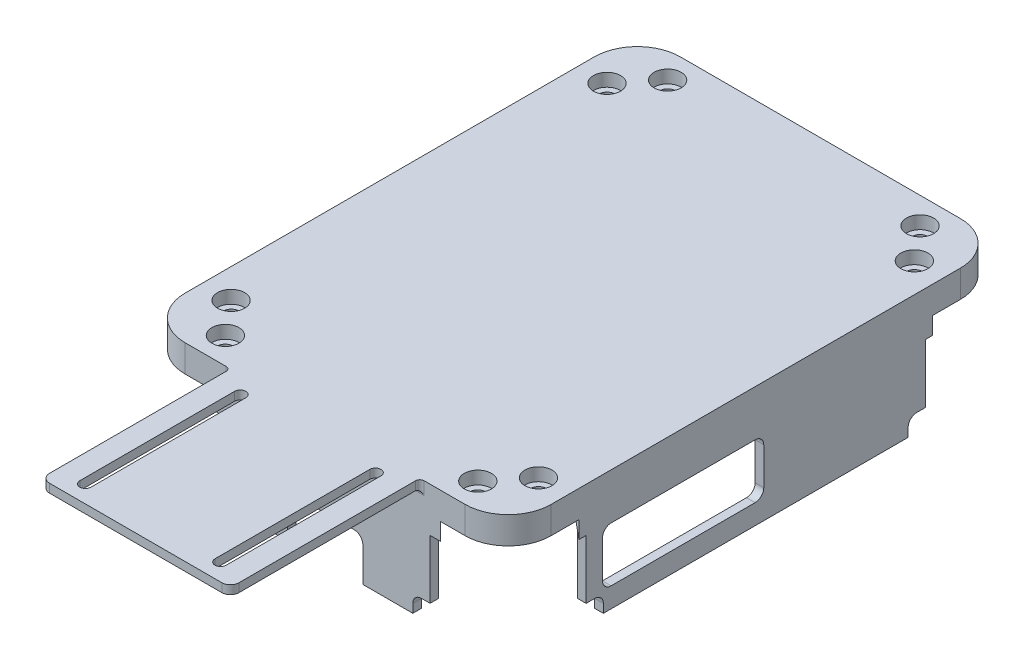
SolidWorks part; units mm, degrees
note: '?' marks a value the reader was unsure of.
material "3-D Printed ABS"
ref_plane "Front Plane" through (0, 0, 0) normal (0, 0, 1) x (1, 0, 0)
ref_plane "Top Plane" through (0, 0, 0) normal (0, 1, 0) x (1, 0, 0)
ref_plane "Right Plane" through (0, 0, 0) normal (1, 0, 0) x (0, 0, -1)
sketch "Sketch1" plane through (0, 0, 0) normal (0, 1, 0) x (1, 0, 0)
  line L1 (-53.975, -73.025) -> (53.975, -73.025)
  line L2 (-53.975, -73.025) -> (-53.975, 73.025)
  line L3 (-53.975, 73.025) -> (53.975, 73.025)
  line L4 (53.975, -73.025) -> (53.975, 73.025)
  line L5 (-53.975, -73.025) -> (53.975, 73.025) construction
  line L6 (-53.975, 73.025) -> (53.975, -73.025) construction
  point P0 (0, 0)
  dimension "D1" = 107.95
  dimension "D2" = 146.05
extrude "Boss-Extrude1" add sketch "Sketch1" against normal blind 2.54
sketch "Sketch13" plane through (0, 0, 0) normal (0, 1, 0) x (1, 0, 0)
  line L0 (0, 155.0212) -> (0, -155.0212) construction
  line L1 (0, 0) -> (-92.0171, 0) construction
  line L2 (53.975, -73.025) -> (53.975, 73.025) construction
  line L3 (53.975, -73.025) -> (28.575, -73.025)
  line L4 (53.975, -73.025) -> (53.975, -47.625)
  line L5 (53.975, -47.625) -> (28.575, -47.625)
  line L6 (28.575, -73.025) -> (28.575, -47.625)
  line L7 (-53.975, -73.025) -> (53.975, -73.025) construction
  line L8 (-28.575, -73.025) -> (-28.575, -47.625)
  line L9 (-53.975, -47.625) -> (-28.575, -47.625)
  line L10 (-53.975, -73.025) -> (-53.975, -47.625)
  line L11 (-53.975, -73.025) -> (-28.575, -73.025)
  line L12 (-53.975, 73.025) -> (-28.575, 73.025)
  line L13 (-53.975, 73.025) -> (-53.975, 47.625)
  line L14 (-53.975, 47.625) -> (-28.575, 47.625)
  line L15 (-28.575, 73.025) -> (-28.575, 47.625)
  line L16 (28.575, 73.025) -> (28.575, 47.625)
  line L17 (53.975, 47.625) -> (28.575, 47.625)
  line L18 (53.975, 73.025) -> (53.975, 47.625)
  line L19 (53.975, 73.025) -> (28.575, 73.025)
  dimension "D1" = 25.4
  dimension "D2" = 25.4
extrude "Boss-Extrude4" add sketch "Sketch13" against normal blind 13.0835
sketch "Sketch2" plane through (0, 0, 0) normal (0, 1, 0) x (1, 0, 0)
  line L0 (0, 0) -> (100.1618, 0) construction
  line L1 (0, 0) -> (0, 86.3534) construction
  line L2 (53.975, 73.025) -> (-53.975, 73.025) construction
  line L3 (-53.975, 73.025) -> (-53.975, -73.025) construction
  line L4 (0, 0) -> (-53.975, 73.025) construction
  line L5 (0, 0) -> (-152.4, 0) construction
  line L6 (-152.4, 0) -> (-152.4, 152.4) construction
  line L7 (-152.4, 152.4) -> (0, 152.4) construction
  line L8 (0, 152.4) -> (0, 86.3534) construction
  line L9 (-152.4, 152.4) -> (0, 0) construction
  line L10 (-152.4, 152.4) -> (-41.275, 60.325) construction
  line L11 (-41.275, 60.325) -> (0, 26.1257) construction
  line L13 (-53.975, 44.9974) -> (-30.7521, 73.025) construction
  circle A0 centre (45.3264, 55.4354) radius 3.302
  circle A1 centre (37.2236, 65.2146) radius 3.302
  circle A2 centre (45.3264, -55.4354) radius 3.302
  circle A3 centre (37.2236, -65.2146) radius 3.302
  circle A4 centre (-37.2236, 65.2146) radius 3.302
  circle A5 centre (-45.3264, 55.4354) radius 3.302
  circle A6 centre (-45.3264, -55.4354) radius 3.302
  circle A7 centre (-37.2236, -65.2146) radius 3.302
  point P15 (-41.275, 60.325)
  dimension "D1" = 6.35
  dimension "D3" = 12.7
  dimension "D4" = 6.604
  dimension "D5" = 6.604
  dimension "D2" = 12.7
  dimension "D6" = 6.35
extrude "Cut-Extrude1" cut sketch "Sketch2" against normal through all
sketch "Sketch3" plane through (0, 0, 0) normal (0, 1, 0) x (1, 0, 0)
  line L0 (-53.975, 25.4) -> (53.975, 25.4) construction
  line L1 (-23.495, 60.325) -> (-19.05, 60.325)
  line L2 (-23.495, 60.325) -> (-23.495, 44.45)
  line L3 (-23.495, 44.45) -> (-19.05, 44.45)
  line L4 (-19.05, 60.325) -> (-19.05, 44.45)
  line L5 (19.05, 60.325) -> (19.05, 44.45)
  line L6 (23.495, 44.45) -> (19.05, 44.45)
  line L7 (23.495, 60.325) -> (23.495, 44.45)
  line L8 (23.495, 60.325) -> (19.05, 60.325)
  line L9 (-53.975, 73.025) -> (-53.975, -73.025) construction
  line L10 (53.975, -73.025) -> (53.975, 73.025) construction
  line L11 (0, 0) -> (0, 97.7255) construction
  line L12 (0, 50.8) -> (0, -46.9255) construction
  line L13 (23.495, -9.525) -> (19.05, -9.525)
  line L14 (23.495, -9.525) -> (23.495, 6.35)
  line L15 (23.495, 6.35) -> (19.05, 6.35)
  line L16 (19.05, -9.525) -> (19.05, 6.35)
  line L17 (-19.05, -9.525) -> (-19.05, 6.35)
  line L18 (-23.495, 6.35) -> (-19.05, 6.35)
  line L19 (-23.495, -9.525) -> (-23.495, 6.35)
  line L20 (-23.495, -9.525) -> (-19.05, -9.525)
  dimension "D1" = 15.875
  dimension "D2" = 4.445
  dimension "D3" = 19.05
  dimension "D4" = 25.4
  dimension "D5" = 44.45
extrude "Cut-Extrude2" [suppressed] cut sketch "Sketch3" against normal through all
fillet "Fillet1" radius 12.7 4 edges at (53.975, -6.5418, -73.025) (53.975, -6.5418, 73.025) (-53.975, -6.5418, 73.025) (-53.975, -6.5418, -73.025)
sketch "Sketch4" plane through (0, 0, 0) normal (0, 1, 0) x (1, 0, 0)
  line L0 (0, 0) -> (80.9727, -80.9727) construction
  line L1 (0, 0) -> (-80.9727, -80.9727) construction
  line L2 (69.1118, -51.1513) -> (28.7006, -10.7401)
  line L3 (28.7006, -10.7401) -> (10.7401, -28.7006)
  line L4 (10.7401, -28.7006) -> (51.1513, -69.1118)
  line L5 (51.1513, -69.1118) -> (69.1118, -51.1513)
  line L6 (0, 0) -> (0, -118.7381) construction
  line L7 (0, 0) -> (-98.4177, 0) construction
  line L8 (-51.1513, -69.1118) -> (-69.1118, -51.1513)
  line L9 (-69.1118, -51.1513) -> (-28.7006, -10.7401)
  line L10 (-28.7006, -10.7401) -> (-10.7401, -28.7006)
  line L11 (-10.7401, -28.7006) -> (-51.1513, -69.1118)
  line L12 (-69.1118, 51.1513) -> (-28.7006, 10.7401)
  line L13 (-51.1513, 69.1118) -> (-69.1118, 51.1513)
  line L14 (-10.7401, 28.7006) -> (-51.1513, 69.1118)
  line L15 (-28.7006, 10.7401) -> (-10.7401, 28.7006)
  line L16 (51.1513, 69.1118) -> (69.1118, 51.1513)
  line L17 (69.1118, 51.1513) -> (28.7006, 10.7401)
  line L18 (28.7006, 10.7401) -> (10.7401, 28.7006)
  line L19 (10.7401, 28.7006) -> (51.1513, 69.1118)
  point P6 (19.7204, -19.7204)
  dimension "D1" = 25.4
  dimension "D2" = 57.15
  dimension "D3" = 45
extrude "Cut-Extrude3" [suppressed] cut sketch "Sketch4" against normal blind 1.5875
sketch "Sketch6" [suppressed] plane through (0, 0, 0) normal (0, 1, 0) x (1, 0, 0)
  line L0 (46.3377, -44.1074) -> (34.6634, -32.4331) construction
  line L1 (0, 0) -> (0, -117.7376) construction
  line L2 (0, 0) -> (-151.7285, 0) construction
  line L4 (28.1601, -10.1996) -> (10.1996, -28.1601) construction
  line L5 (50.6107, -68.5712) -> (68.5712, -50.6107) construction
  text T0 "ESC" font "Century Gothic" height in points 22
  dimension "D1" = 45
  dimension "D2" = 20.32
  dimension "D3" = 20.32
extrude "Cut-Extrude5" [suppressed] cut sketch "Sketch6" against normal blind 3.175
sketch "Sketch5" plane through (0, 0, 0) normal (0, 1, 0) x (1, 0, 0)
  line L0 (41.275, 73.025) -> (-41.275, 73.025) construction
  line L1 (14.2875, 15.875) -> (-14.2875, 15.875)
  line L2 (14.2875, 15.875) -> (14.2875, 66.675)
  line L3 (14.2875, 66.675) -> (-14.2875, 66.675)
  line L4 (-14.2875, 15.875) -> (-14.2875, 66.675)
  point P4 (0, 15.875)
  dimension "D1" = 50.8
  dimension "D2" = 28.575
  dimension "D3" = 6.35
extrude "Cut-Extrude4" [suppressed] cut sketch "Sketch5" against normal blind 1.5875
ref_axis "Axis1" through (0, 0.3175, 0) along (0, -1, 0)?
pattern_circular "CirPattern1" [suppressed] count 4 over 360 about axis through (0, 0.3175, 0) along (0, -1, 0)
sketch "Sketch7" plane through (0, 0, 0) normal (0, 1, 0) x (1, 0, 0)
  line L0 (0, 0) -> (0, -54.962) construction
  line L1 (63.4018, -13.3522) -> (38.0018, -13.3522)
  line L2 (63.4018, -13.3522) -> (63.4018, 43.7978)
  line L3 (63.4018, 43.7978) -> (38.0018, 43.7978)
  line L4 (38.0018, -13.3522) -> (38.0018, 43.7978)
  line L5 (-38.0018, -13.3522) -> (-38.0018, 43.7978)
  line L6 (-63.4018, 43.7978) -> (-38.0018, 43.7978)
  line L7 (-63.4018, -13.3522) -> (-63.4018, 43.7978)
  line L8 (-63.4018, -13.3522) -> (-38.0018, -13.3522)
  line L9 (-41.275, -73.025) -> (41.275, -73.025) construction
  line L10 (38.5677, -40.64) -> (-18.5823, -40.64)
  line L11 (38.5677, -40.64) -> (38.5677, -66.04)
  line L12 (38.5677, -66.04) -> (-18.5823, -66.04)
  line L13 (-18.5823, -40.64) -> (-18.5823, -66.04)
  line L14 (38.5677, -40.64) -> (-18.5823, -66.04) construction
  line L15 (38.5677, -66.04) -> (-18.5823, -40.64) construction
  line L16 (19.844, -36.1003) -> (-37.306, -36.1003)
  line L17 (19.844, -36.1003) -> (19.844, -61.5003)
  line L18 (19.844, -61.5003) -> (-37.306, -61.5003)
  line L19 (-37.306, -36.1003) -> (-37.306, -61.5003)
  line L20 (19.844, -36.1003) -> (-37.306, -61.5003) construction
  line L21 (19.844, -61.5003) -> (-37.306, -36.1003) construction
  point P11 (9.9927, -53.34)
  point P18 (-8.731, -48.8003)
  dimension "D1" = 57.15
  dimension "D2" = 25.4
  dimension "D3" = 57.15
  dimension "D4" = 25.4
  dimension "D5" = 6.985
  dimension "D6" = 57.15
  dimension "D7" = 25.4
extrude "Cut-Extrude6" [suppressed] cut sketch "Sketch7" against normal blind 1.27
sketch "Sketch8" plane through (0, 0, 0) normal (0, 1, 0) x (1, 0, 0)
  line L7 (19.05, -31.75) -> (-19.05, -31.75)
  line L8 (19.05, -31.75) -> (19.05, 31.75)
  line L9 (19.05, 31.75) -> (-19.05, 31.75)
  line L10 (-19.05, -31.75) -> (-19.05, 31.75)
  point P0 (0, 0)
  dimension "D1" = 38.1
  dimension "D2" = 31.75
  dimension "D3" = 63.5
extrude "Boss-Extrude3" [suppressed] add sketch "Sketch8" along normal blind 2.54
sketch "Sketch11" plane through (0, 0, 0) normal (0, 1, 0) x (1, 0, 0)
  line L1 (19.05, -9.525) -> (-19.05, -9.525)
  line L2 (19.05, -9.525) -> (19.05, 6.35)
  line L3 (19.05, 6.35) -> (-19.05, 6.35)
  line L4 (-19.05, -9.525) -> (-19.05, 6.35)
extrude "Cut-Extrude9" [suppressed] cut sketch "Sketch11" against normal mid plane 2.54
sketch "Sketch12" [suppressed] plane through (0, 0, 0) normal (0, 1, 0) x (1, 0, 0)
  line L0 (-23.495, -9.525) -> (-19.05, -9.525) construction
  line L1 (12.7, -9.525) -> (-12.7, -9.525)
  line L2 (12.7, -9.525) -> (12.7, 6.35)
  line L3 (12.7, 6.35) -> (-12.7, 6.35)
  line L4 (-12.7, -9.525) -> (-12.7, 6.35)
  line L5 (-19.05, 6.35) -> (-23.495, 6.35) construction
  line L6 (19.05, 52.3875) -> (-19.05, 52.3875) construction
  line L7 (19.05, 60.325) -> (19.05, 44.45) construction
  line L8 (-19.05, 44.45) -> (-19.05, 60.325) construction
  line L9 (-12.7, 114.3) -> (-12.7, 98.425)
  line L10 (12.7, 98.425) -> (-12.7, 98.425)
  line L11 (12.7, 114.3) -> (12.7, 98.425)
  line L12 (12.7, 114.3) -> (-12.7, 114.3)
  point P8 (0, -9.525)
  dimension "D1" = 25.4
extrude "Cut-Extrude12" [suppressed] cut sketch "Sketch12" along normal through all
sketch "Sketch9" plane through (0, 0, 0) normal (0, 1, 0) x (1, 0, 0)
  line L1 (25.1579, -52.4084) -> (-25.6421, -52.4084)
  line L2 (25.1579, -52.4084) -> (25.1579, -1.6084)
  line L3 (25.1579, -1.6084) -> (-25.6421, -1.6084)
  line L4 (-25.6421, -52.4084) -> (-25.6421, -1.6084)
  line L5 (25.1579, -52.4084) -> (-25.6421, -1.6084) construction
  line L6 (25.1579, -1.6084) -> (-25.6421, -52.4084) construction
  point P0 (-0.2421, -27.0084)
  dimension "D1" = 50.8
  dimension "D2" = 50.8
fillet "Fillet2" [suppressed] radius 12.7
sketch "Sketch14" plane through (0, -13.0835, 0) normal (0, -1, 0) x (1, 0, 0)
  line L0 (0, 0) -> (0, -152.4) construction
  line L1 (0, 0) -> (152.4, 0) construction
  line L2 (0, 0) -> (152.4, -152.4) construction
  line L3 (152.4, -152.4) -> (41.275, -60.325) construction
  line L4 (41.275, -60.325) -> (31.0918, -51.8875) construction
  line L5 (31.0918, -51.8875) -> (0, -26.1257) construction
  line L6 (24.7418, -27.9081) -> (6.35, -50.1051)
  line L7 (6.35, -50.1051) -> (137.0133, -158.369)
  line L8 (137.0133, -158.369) -> (155.4051, -136.172)
  line L9 (155.4051, -136.172) -> (24.7418, -27.9081)
  line L10 (-24.7418, -27.9081) -> (-6.35, -50.1051)
  line L11 (-155.4051, -136.172) -> (-24.7418, -27.9081)
  line L12 (-6.35, -50.1051) -> (-137.0133, -158.369)
  line L13 (-137.0133, -158.369) -> (-155.4051, -136.172)
  line L14 (-155.4051, 136.172) -> (-24.7418, 27.9081)
  line L15 (-137.0133, 158.369) -> (-155.4051, 136.172)
  line L16 (-6.35, 50.1051) -> (-137.0133, 158.369)
  line L17 (-24.7418, 27.9081) -> (-6.35, 50.1051)
  line L18 (24.7418, 27.9081) -> (6.35, 50.1051)
  line L19 (137.0133, 158.369) -> (155.4051, 136.172)
  line L20 (155.4051, 136.172) -> (24.7418, 27.9081)
  line L21 (6.35, 50.1051) -> (137.0133, 158.369)
  line L22 (41.275, -73.025) -> (-41.275, -73.025) construction
  line L23 (53.975, 60.325) -> (53.975, -60.325) construction
  point P3 (15.5459, -39.0066)
  point P6 (41.275, -60.325)
  dimension "D1" = 152.4
  dimension "D2" = 152.4
  dimension "D3" = 6.35
  dimension "D4" = 14.4132
  dimension "D5" = 12.7
  dimension "D6" = 12.7
extrude "Cut-Extrude13" cut sketch "Sketch14" against normal blind 5.08
sketch "Sketch15" plane through (0, 0, 0) normal (0, 1, 0) x (1, 0, 0)
  line L0 (0, 0) -> (72.5178, 0) construction
  line L1 (0, 0) -> (0, 124.598) construction
  circle A0 centre (-45.3264, 55.4354) radius 5.08
  circle A1 centre (45.3264, 55.4354) radius 5.08
  circle A2 centre (37.2236, 65.2146) radius 5.08
  circle A3 centre (45.3264, -55.4354) radius 5.08
  circle A4 centre (37.2236, -65.2146) radius 5.08
  circle A5 centre (-37.2236, -65.2146) radius 5.08
  circle A6 centre (-37.2236, 65.2146) radius 5.08
  circle A7 centre (-45.3264, -55.4354) radius 5.08
extrude "Boss-Extrude5" add sketch "Sketch15" against normal offset from surface (5.4635 mm away) 2.54 up to face at (-41.6508, -8.0035, -60.7008)
hole_wizard "M4 Clearance Hole1" [suppressed] positions "Sketch18" profile "Sketch16" hole size "M4" standard "ANSI Metric"
sketch "Sketch18" plane through (0, -19.05, 0) normal (0, -1, 0) x (-1, 0, 0)
  point P0 (41.275, 60.325)
  point P3 (41.275, -60.325)
  point P6 (-41.275, -60.325)
  point P9 (-41.275, 60.325)
sketch "Sketch16" plane through (-41.275, -19.05, -60.325) normal (1, 0, 0) x (0, 0, -1)
  line L0 (0, 0) -> (0, 19.05)
  line L1 (0, 19.05) -> (2.25, 19.05)
  line L2 (2.25, 19.05) -> (2.25, 0)
  line L5 (2.25, 0) -> (0, 0)
  line L11 (0, -6.35) -> (0, 107.95) construction
  dimension "Thru Hole Dia." = 4.5
  dimension "Thru Hole Depth" = 19.05
hole_wizard "CBORE for M4 SHCS1" [suppressed] positions "Sketch21" profile "Sketch20" counterbore size "M4" standard "ANSI Metric"
sketch "Sketch21" [suppressed] plane through (0, 0, 0) normal (0, 1, 0) x (1, 0, 0)
  point P0 (41.275, 60.325)
  point P3 (-41.275, 60.325)
  point P6 (-41.275, -60.325)
  point P9 (41.275, -60.325)
sketch "Sketch20" plane through (41.275, 0, -60.325) normal (1, 0, 0) x (0, 0, 1)
  line L0 (0, 0) -> (0, 24.13)
  line L1 (0, 24.13) -> (2.25, 24.13)
  line L3 (2.25, 24.13) -> (2.25, 4)
  line L4 (2.25, 4) -> (4, 4)
  line L5 (4, 4) -> (4, 0)
  line L7 (4, 0) -> (0, 0)
  line L11 (0, -6.35) -> (0, 107.95) construction
  dimension "Thru Hole Dia." = 4.5
  dimension "Thru Hole Depth" = 24.13
  dimension "C'Bore Dia." = 8
  dimension "C'Bore Depth" = 4
sketch "Sketch23" plane through (0, -8.0035, 0) normal (0, -1, 0) x (1, 0, 0)
  circle A0 centre (-45.3264, -55.4354) radius 2.25
  circle A1 centre (-37.2236, -65.2146) radius 2.25
  dimension "D1" = 4.5
  dimension "D2" = 4.5
extrude "Cut-Extrude14" cut sketch "Sketch23" against normal through all
sketch "Sketch24" plane through (0, 0, 0) normal (0, 1, 0) x (1, 0, 0)
  circle A0 centre (-45.3264, 55.4354) radius 4
  circle A1 centre (-37.2236, 65.2146) radius 4
  dimension "D1" = 8
  dimension "D2" = 8
extrude "Cut-Extrude15" cut sketch "Sketch24" against normal blind 3.81
mirror "Mirror1" about plane through (0, 0, 0) normal (0, 0, 1) of "Cut-Extrude15", "Cut-Extrude14"
mirror "Mirror2" about plane through (0, 0, 0) normal (1, 0, 0) of "Cut-Extrude15", "Cut-Extrude14", "Mirror1"
fillet "Fillet3" radius 12.7 4 edges at (-28.575, -5.2718, -47.625) (28.575, -5.2718, -47.625) (28.575, -5.2718, 47.625) (-28.575, -5.2718, 47.625)
sketch "Sketch25" plane through (0, 0, 0) normal (0, 1, 0) x (1, 0, 0)
  line L0 (0, 0) -> (0, -33.9706) construction
  line L1 (0, 0) -> (63.8751, 0) construction
  circle A0 centre (30.0609, 0) radius 3.4925
  circle A1 centre (30.0609, -24.9682) radius 3.4925
  circle A2 centre (30.0609, 24.9682) radius 3.4925
  circle A3 centre (-30.0609, 24.9682) radius 3.4925
  circle A4 centre (-30.0609, -24.9682) radius 3.4925
  circle A5 centre (-30.0609, 0) radius 3.4925
  dimension "D1" = 6.985
  dimension "D2" = 6.985
  dimension "D3" = 24.9682
  dimension "D4" = 30.0609
extrude "GimbalMount1" [suppressed] cut sketch "Sketch25" against normal through all
sketch "Sketch26" [suppressed] plane through (0, 0, 0) normal (0, 1, 0) x (1, 0, 0)
  circle A0 centre (30.0609, -24.9682) radius 5.715
  circle A1 centre (30.0609, 0) radius 5.715
  circle A2 centre (30.0609, 24.9682) radius 5.715
  circle A3 centre (-30.0609, -24.9682) radius 5.715
  circle A4 centre (-30.0609, 0) radius 5.715
  circle A5 centre (-30.0609, 24.9682) radius 5.715
  dimension "D1" = 11.43
extrude "GimbalMount2" [suppressed] cut sketch "Sketch26" against normal blind 1.524
fillet "Fillet4" radius 1.016 8 edges at (-45.3264, -8.0035, 52.1334) (-37.2236, -8.0035, 61.9126) (37.2236, -8.0035, 68.5166) (45.3264, -8.0035, 58.7374) (-45.3264, -8.0035, -52.1334) (-37.2236, -8.0035, -61.9126) (37.2236, -8.0035, -68.5166) (45.3264, -8.0035, -58.7374)
sketch "Sketch27" plane through (0, -2.54, 0) normal (0, -1, 0) x (1, 0, 0)
  line L1 (30.9464, -73.025) -> (-30.9464, -73.025)
  line L2 (30.9464, -73.025) -> (30.9464, -70.485)
  line L3 (30.9464, -70.485) -> (-30.9464, -70.485)
  line L4 (-30.9464, -73.025) -> (-30.9464, -70.485)
  line L6 (0, 0) -> (0, -45.0707) construction
  line L7 (0, 0) -> (-77.1364, 0) construction
  line L8 (-30.9464, 73.025) -> (-30.9464, 70.485)
  line L9 (30.9464, 70.485) -> (-30.9464, 70.485)
  line L10 (30.9464, 73.025) -> (30.9464, 70.485)
  line L11 (30.9464, 73.025) -> (-30.9464, 73.025)
  line L13 (53.975, -50.0253) -> (51.435, -50.0253)
  line L14 (53.975, -50.0253) -> (53.975, 50.0253)
  line L15 (53.975, 50.0253) -> (51.435, 50.0253)
  line L16 (51.435, -50.0253) -> (51.435, 50.0253)
  line L17 (-51.435, -50.0253) -> (-51.435, 50.0253)
  line L18 (-53.975, 50.0253) -> (-51.435, 50.0253)
  line L19 (-53.975, -50.0253) -> (-53.975, 50.0253)
  line L20 (-53.975, -50.0253) -> (-51.435, -50.0253)
  line L22 (28.575, -68.5201) -> (34.0119, -73.025) construction
  line L23 (-34.0119, -73.025) -> (-28.575, -68.5201) construction
  line L24 (28.575, -73.025) -> (-28.575, -73.025) construction
  line L25 (53.975, -52.1299) -> (48.5381, -47.625) construction
  line L26 (53.975, 47.625) -> (53.975, -47.625) construction
  line L27 (48.5381, 47.625) -> (53.975, 52.1299) construction
  dimension "D1" = 2.54
  dimension "D2" = 2.54
extrude "Boss-Extrude6" add sketch "Sketch27" along normal blind 32.9882
sketch "Sketch28" plane through (0, 0, -73.025) normal (0, 0, -1) x (-1, 0, 0)
  line L0 (-41.275, 0) -> (41.275, 0) construction
  line L1 (-17.526, -35.5282) -> (17.526, -35.5282)
  line L2 (-16.891, -27.9082) -> (-16.891, -20.6058)
  line L3 (-14.351, -18.0657) -> (14.351, -18.0657)
  line L4 (16.891, -27.9082) -> (16.891, -20.6058)
  line L5 (30.9464, -35.5282) -> (-30.9464, -35.5282) construction
  line L6 (19.431, -30.4482) -> (27.051, -30.4482)
  line L7 (0, -18.0657) -> (0, 0) construction
  line L8 (17.526, -35.5282) -> (29.591, -35.5282)
  line L9 (29.591, -32.9882) -> (29.591, -35.5282)
  line L11 (-19.431, -30.4482) -> (-27.051, -30.4482)
  line L13 (-17.526, -35.5282) -> (-29.591, -35.5282)
  line L14 (-29.591, -32.9882) -> (-29.591, -35.5282)
  arc A0 (-29.591, -32.9882) -> (-27.051, -30.4482) centre (-27.051, -32.9882) cw
  arc A1 (-19.431, -30.4482) -> (-16.891, -27.9082) centre (-19.431, -27.9082) ccw
  arc A2 (-16.891, -20.6058) -> (-14.351, -18.0657) centre (-14.351, -20.6058) cw
  arc A3 (14.351, -18.0657) -> (16.891, -20.6058) centre (14.351, -20.6058) cw
  arc A4 (16.891, -27.9082) -> (19.431, -30.4482) centre (19.431, -27.9082) ccw
  arc A5 (27.051, -30.4482) -> (29.591, -32.9882) centre (27.051, -32.9882) cw
  point P5 (0, -35.5282)
  point P19 (-29.591, -30.4482)
  point P25 (-16.891, -18.0657)
  point P28 (16.891, -18.0657)
  point P34 (29.591, -30.4482)
  dimension "D7" = 2.54
  dimension "D1" = 17.4625
  dimension "D2" = 33.782
  dimension "D3" = 10.16
  dimension "D4" = 5.08
  dimension "D5" = 10.16
  dimension "D6" = 5.08
extrude "Cut-Extrude16" cut sketch "Sketch28" against normal blind 41.656
sketch "Sketch29" plane through (-53.975, 0, 0) normal (-1, 0, 0) x (0, 0, 1)
  line L0 (0, -35.5282) -> (0, -17.4257) construction
  line L1 (-50.0253, -35.5282) -> (-44.9453, -35.5283)
  line L2 (-50.0253, -35.5282) -> (-50.0253, -30.4482)
  line L3 (-50.0253, -30.4482) -> (-47.4853, -30.4482)
  line L4 (-44.9453, -35.5283) -> (-44.9453, -32.9882)
  line L5 (50.0253, -35.5282) -> (-50.0253, -35.5282) construction
  line L6 (44.9453, -35.5283) -> (44.9453, -32.9882)
  line L7 (50.0253, -30.4482) -> (47.4853, -30.4482)
  line L8 (50.0253, -35.5282) -> (50.0253, -30.4482)
  line L9 (50.0253, -35.5282) -> (44.9453, -35.5283)
  arc A0 (-44.9453, -32.9882) -> (-47.4853, -30.4482) centre (-47.4853, -32.9882) ccw
  arc A1 (44.9453, -32.9882) -> (47.4853, -30.4482) centre (47.4853, -32.9882) cw
  dimension "D1" = 2.54
  dimension "D2" = 5.08
  dimension "D3" = 5.08
extrude "Cut-Extrude17" cut sketch "Sketch29" against normal through all
sketch "Sketch30" plane through (0, 0, 73.025) normal (0, 0, 1) x (1, 0, 0)
  line L0 (0, -35.5282) -> (0, -22.969) construction
  line L1 (-30.9464, -35.5282) -> (-25.8664, -35.5282)
  line L2 (-30.9464, -35.5282) -> (-30.9464, -30.4482)
  line L3 (-30.9464, -30.4482) -> (-28.4064, -30.4482)
  line L4 (-25.8664, -35.5282) -> (-25.8664, -32.9882)
  line L5 (30.9464, -35.5282) -> (-30.9464, -35.5282) construction
  line L6 (25.8664, -35.5282) -> (25.8664, -32.9882)
  line L7 (30.9464, -30.4482) -> (28.4064, -30.4482)
  line L8 (30.9464, -35.5282) -> (30.9464, -30.4482)
  line L9 (30.9464, -35.5282) -> (25.8664, -35.5282)
  arc A0 (-25.8664, -32.9882) -> (-28.4064, -30.4482) centre (-28.4064, -32.9882) ccw
  arc A1 (25.8664, -32.9882) -> (28.4064, -30.4482) centre (28.4064, -32.9882) cw
  dimension "D1" = 2.54
  dimension "D2" = 5.08
  dimension "D3" = 5.08
extrude "Cut-Extrude18" cut sketch "Sketch30" against normal through all
sketch "Sketch31" plane through (0, 0, 73.025) normal (0, 0, 1) x (1, 0, 0)
  line L0 (25.8664, -35.5282) -> (-25.8664, -35.5282) construction
  line L1 (-11.1125, -35.5282) -> (11.1125, -35.5282)
  line L2 (-11.1125, -35.5282) -> (-11.1125, -22.8282)
  line L3 (-11.1125, -22.8282) -> (11.1125, -22.8282)
  line L4 (11.1125, -35.5282) -> (11.1125, -22.8282)
  line L5 (0, -22.8282) -> (0, -15.4197) construction
  line L6 (-41.275, 0) -> (41.275, 0) construction
  point P10 (0, 0)
  dimension "D1" = 12.7
  dimension "D2" = 22.225
extrude "Cut-Extrude19" cut sketch "Sketch31" against normal up to next
fillet "Fillet5" radius 2.54 2 edges at (11.1125, -22.8282, 71.755) (-11.1125, -22.8282, 71.755)
sketch "Sketch33" plane through (0, 0, 0) normal (0, 1, 0) x (1, 0, 0)
  line L0 (0, 0) -> (0, -73.025) construction
  line L1 (-41.275, -73.025) -> (41.275, -73.025) construction
  line L2 (0, -73.025) -> (-41.275, -73.025) construction
  line L3 (0, -73.025) -> (41.275, -73.025) construction
  line L4 (-27.94, -73.025) -> (0, -73.025)
  line L5 (0, -73.025) -> (27.94, -73.025)
  line L6 (0, -73.025) -> (0, -100.965) construction
  line L7 (0, -100.965) -> (0, -128.905) construction
  line L8 (0, -128.905) -> (-27.94, -128.905) construction
  line L9 (-27.94, -128.905) -> (-27.94, -100.965) construction
  line L10 (-27.94, -100.965) -> (-27.94, -73.025) construction
  line L11 (0, -128.905) -> (27.94, -128.905) construction
  line L12 (27.94, -128.905) -> (27.94, -100.965) construction
  line L13 (27.94, -100.965) -> (27.94, -73.025) construction
  line L14 (-27.94, -100.965) -> (27.94, -100.965) construction
  line L15 (27.94, -73.025) -> (27.94, -100.965)
  line L16 (27.94, -100.965) -> (27.94, -126.365)
  line L17 (25.4, -128.905) -> (0, -128.905)
  line L18 (0, -128.905) -> (-25.4, -128.905)
  line L19 (-27.94, -126.365) -> (-27.94, -100.965)
  line L20 (-27.94, -100.965) -> (-27.94, -73.025)
  line L21 (-19.939, -78.1385) -> (-19.939, -123.7915) construction
  line L22 (-18.288, -78.1385) -> (-18.288, -123.7915)
  line L23 (-21.59, -78.1385) -> (-21.59, -123.7915)
  line L24 (19.939, -78.1385) -> (19.939, -123.7915) construction
  line L25 (18.288, -78.1385) -> (18.288, -123.7915)
  line L26 (21.59, -78.1385) -> (21.59, -123.7915)
  arc A0 (-18.288, -78.1385) -> (-21.59, -78.1385) centre (-19.939, -78.1385) ccw
  arc A1 (-21.59, -123.7915) -> (-18.288, -123.7915) centre (-19.939, -123.7915) ccw
  arc A2 (18.288, -78.1385) -> (21.59, -78.1385) centre (19.939, -78.1385) cw
  arc A3 (21.59, -123.7915) -> (18.288, -123.7915) centre (19.939, -123.7915) cw
  arc A4 (27.94, -126.365) -> (25.4, -128.905) centre (25.4, -126.365) cw
  arc A5 (-25.4, -128.905) -> (-27.94, -126.365) centre (-25.4, -126.365) cw
  point P20 (-19.939, -100.965)
  point P26 (19.939, -100.965)
  dimension "D6" = 2.54
  dimension "D1" = 27.94
  dimension "D2" = 27.94
  dimension "D3" = 55.88
  dimension "D4" = 6.35
  dimension "D5" = 3.302
extrude "Boss-Extrude7" add sketch "Sketch33" against normal blind 2.54
fillet "Fillet6" radius 1.27 1 edges at (0, -2.54, 73.025)
fillet "Fillet7" radius 1.27 2 edges at (27.94, -1.905, 73.025) (-27.94, -1.905, 73.025)
sketch "Sketch34" plane through (-53.975, 0, 0) normal (-1, 0, 0) x (0, 0, 1)
  line L1 (0.1763, -13.587) -> (42.6517, -13.587)
  line L2 (-2.3637, -16.127) -> (-2.3637, -27.0912)
  line L3 (0.1763, -29.6312) -> (42.6517, -29.6312)
  line L4 (45.1917, -16.127) -> (45.1917, -27.0912)
  arc A0 (42.6517, -29.6312) -> (45.1917, -27.0912) centre (42.6517, -27.0912) ccw
  arc A1 (42.6517, -13.587) -> (45.1917, -16.127) centre (42.6517, -16.127) cw
  arc A2 (0.1763, -13.587) -> (-2.3637, -16.127) centre (0.1763, -16.127) ccw
  arc A3 (-2.3637, -27.0912) -> (0.1763, -29.6312) centre (0.1763, -27.0912) ccw
  dimension "D1" = 2.54
extrude "Cut-Extrude20" cut sketch "Sketch34" against normal blind 128.27 and the other way blind 9.398
equation "\"Plate Thickness\"= \"Plate Thickness@Quad Assemb.sldasm\""
equation "\"D1@Boss-Extrude1\"=\"Plate Thickness\""
equation "\"Plate Dim X\"= \"Plate Dim X@Quad Assemb.sldasm\""
equation "\"Plate Dim Y\"= \"Plate Dim Y@Quad Assemb.sldasm\""
equation "\"D1@Boss-Extrude4\"= \"Component Y@Quad Assemb.sldasm\" - \"ArmBase@Arm V4-1.Part\""
equation "\"D4@Sketch14\" = \"ArmBase@Arm V4-1.Part\" / 2 + .005"
equation "\"Dowell Width\"= \"Dowell Width@Quad Assemb.sldasm\""
equation "\"D1@Sketch2\"=\"Dowell Width\""
equation "\"Dowell Height\"= \"Dowell Height@Quad Assemb.sldasm\""
equation "\"D1@Boss-Extrude5\"=\"Dowell Height\""
equation "\"GimbalMount1\"= if ( \"Gimbal Mount@Quad Assemb.sldasm\" = 1 , \"unsuppressed\" , \"suppressed\" )"
equation "\"GimbalMount2\"= if ( \"Gimbal Mount@Quad Assemb.sldasm\" = 1 , \"unsuppressed\" , \"suppressed\" )"
equation "\"D1@Boss-Extrude6\"=\"Component Y@Quad Assemb.sldasm\"-.31-1/32in"
equation "\"D1@Sketch28\"=\"radio rx Z@Quad Assemb.sldasm\"+3/16"
equation "\"D2@Sketch28\"=\"radio rx x@quad assemb.sldasm\"+.2"
equation "\"D4@Sketch2\"=\"Dowell Width\"+0.01in"
equation "\"D5@Sketch2\"=\"Dowell Width\"+0.01in"
equation "\"D6@Sketch2\"=\"Dowell Width\""
